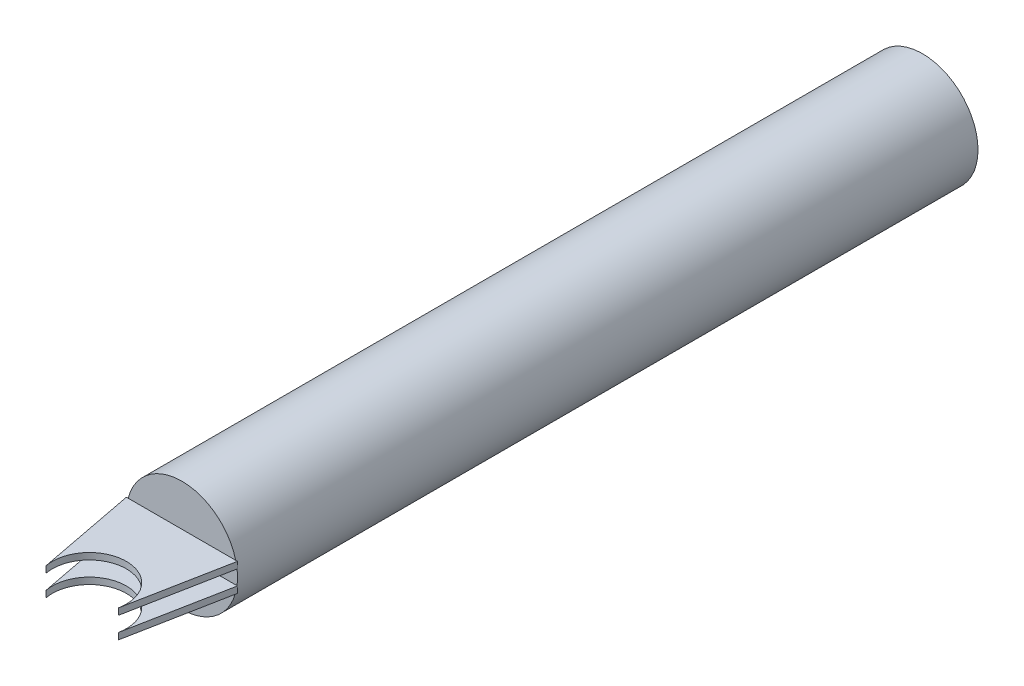
SolidWorks part; units mm, degrees
ref_plane "Front Plane" through (0, 0, 0) normal (0, 0, 1) x (1, 0, 0)
ref_plane "Top Plane" through (0, 0, 0) normal (0, 1, 0) x (1, 0, 0)
ref_plane "Right Plane" through (0, 0, 0) normal (1, 0, 0) x (0, 0, -1)
sketch "Pole Sketch" plane through (0, 0, 0) normal (0, 0, 1) x (1, 0, 0)
  circle A0 centre (0, 0) radius 30
  dimension "D1" = 60
extrude "Pole Extrude" add sketch "Pole Sketch" against normal blind 400
sketch "Palm Holder Sketch" plane through (0, 0, 0) normal (0, 1, 0) x (1, 0, 0)
  line L0 (19.6389, -53.7833) -> (30, 0)
  line L1 (30, 0) -> (-30, 0)
  line L2 (-30, 0) -> (-19.6389, -53.7833)
  line L4 (19.6389, -53.7833) -> (-19.6389, -53.7833) construction
  arc A0 (19.6389, -53.7833) -> (-19.6389, -53.7833) centre (0, -50) ccw
  dimension "D1" = 40
  dimension "D2" = 50
extrude "Upper Palm Holder Extrude" add sketch "Palm Holder Sketch" along normal blind 3.5 from offset 4
extrude "Lower Palm Holder Extrude" add sketch "Palm Holder Sketch<2>" against normal blind 3.5 from offset 4 offset against normal yes
sketch "Palm Holder Sketch<2>" plane through (0, 0, 0) normal (0, 1, 0) x (1, 0, 0) same geometry as "Palm Holder Sketch"
